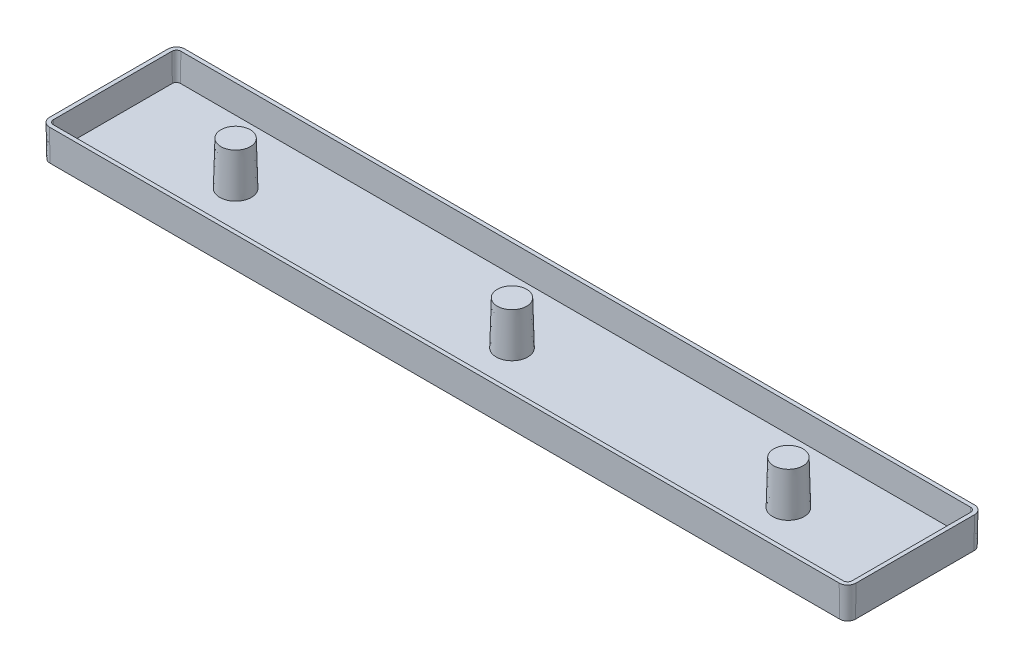
SolidWorks part; units mm, degrees
ref_plane "Front Plane" through (0, 0, 0) normal (0, 0, 1) x (1, 0, 0)
ref_plane "Top Plane" through (0, 0, 0) normal (0, 1, 0) x (1, 0, 0)
ref_plane "Right Plane" through (0, 0, 0) normal (1, 0, 0) x (0, 0, -1)
sketch "Sketch1" plane through (0, 0, 0) normal (0, 1, 0) x (1, 0, 0)
  line L1 (-50, -8.5) -> (50, -8.5)
  line L2 (-51, -7.5) -> (-51, 7.5)
  line L3 (-50, 8.5) -> (50, 8.5)
  line L4 (51, -7.5) -> (51, 7.5)
  line L5 (-51, -8.5) -> (51, 8.5) construction
  line L6 (-51, 8.5) -> (51, -8.5) construction
  arc A0 (-51, 7.5) -> (-50, 8.5) centre (-50, 7.5) cw
  arc A1 (51, 7.5) -> (50, 8.5) centre (50, 7.5) ccw
  arc A2 (51, -7.5) -> (50, -8.5) centre (50, -7.5) cw
  arc A3 (-50, -8.5) -> (-51, -7.5) centre (-50, -7.5) cw
  point P0 (0, 0)
  dimension "D3" = 1
  dimension "D1" = 102
  dimension "D2" = 17
extrude "Boss-Extrude1" add sketch "Sketch1" along normal blind 4 draft 1 draft outward yes
shell "Shell1" thickness 0.5 removed face at (0, 4, 0)
sketch "Sketch2" plane through (0, 0.5, 0) normal (0, 1, 0) x (1, 0, 0)
  line L1 (-2.2, 0) -> (2.2, 0) construction
  line L18 (35, 0) -> (35.6, 0) construction
  line L20 (37.8078, 0) -> (55.4489, 0) construction
  circle A12 centre (35, 0) radius 2
  circle A13 centre (0, 0) radius 2
  circle A14 centre (-35, 0) radius 2
  point P12 (35, 0)
  point P13 (-35, 0)
extrude "Boss-Extrude2" add sketch "Sketch2" along normal blind 5.5 draft 1.5
